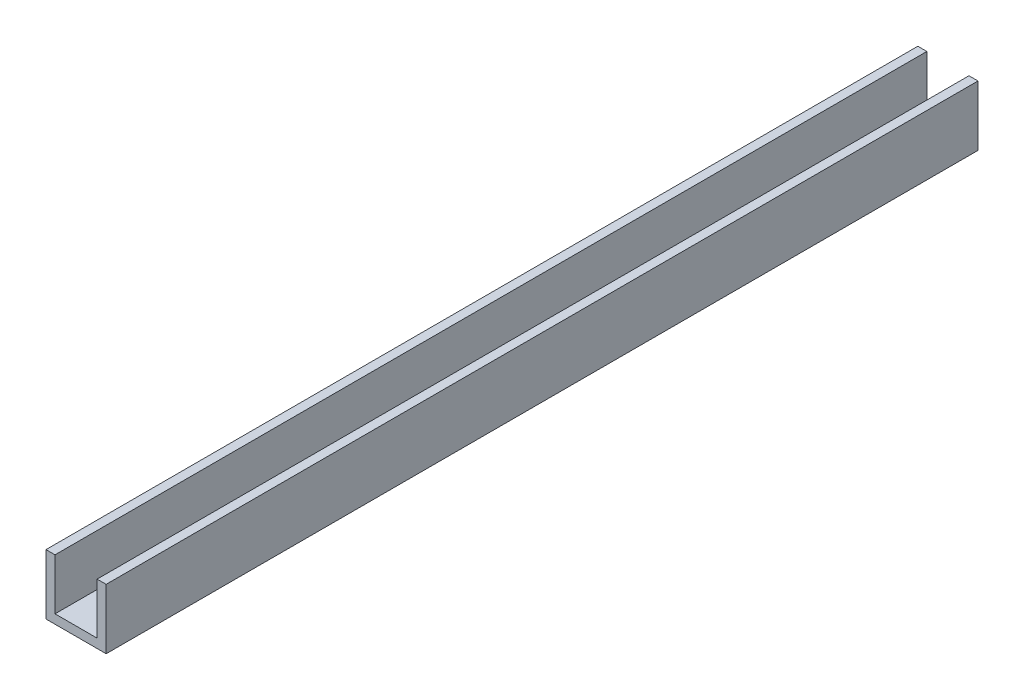
SolidWorks part; units mm, degrees
material "1060 Сплав"
ref_plane "Спереди" through (0, 0, 0) normal (0, 0, 1) x (1, 0, 0)
ref_plane "Сверху" through (0, 0, 0) normal (0, 1, 0) x (1, 0, 0)
ref_plane "Справа" through (0, 0, 0) normal (1, 0, 0) x (0, 0, -1)
sketch "Эскиз1" plane through (0, 0, 0) normal (0, 0, 1) x (1, 0, 0)
  line L0 (0, 0) -> (10, 0)
  line L1 (10, 0) -> (10, 10)
  line L2 (10, 10) -> (8.5, 10)
  line L3 (8.5, 10) -> (8.5, 1.5)
  line L4 (8.5, 1.5) -> (1.5, 1.5)
  line L5 (1.5, 1.5) -> (1.5, 10)
  line L6 (1.5, 10) -> (0, 10)
  line L7 (0, 10) -> (0, 0)
  dimension "D1" = 1.5
  dimension "D2" = 1.5
  dimension "D3" = 10
extrude "Бобышка-Вытянуть1" add sketch "Эскиз1" along normal blind 144.94
sketch "Эскиз2" plane through (10, 0, 0) normal (1, 0, 0) x (0, 0, -1)
  line L0 (-144.94, 5) -> (0, 5) construction
  line L1 (-144.94, 0) -> (-144.94, 10) construction
  line L2 (0, 0) -> (0, 10) construction
ref_axis "Ось1" through (5, 0, 0) along (0, 0, 1)
equation "\"ATX.Case.01.Profile.10.Width\"=10"
equation "\"ATX.Case.01.Profile.10.Thickness\"=1.5"
equation "\"D2@Эскиз1\"= \"ATX.Case.01.Profile.10.Thickness\""
equation "\"D1@Эскиз1\"= \"ATX.Case.01.Profile.10.Thickness\""
equation "\"D3@Эскиз1\"= \"ATX.Case.01.Profile.10.Width\""
equation "\"D1@Бобышка-Вытянуть1\"=\"ATX.Case.01.Dimension.1\" - \"ATX.Case.01.Profile.20.Thickness\" * 2мм * 2"
